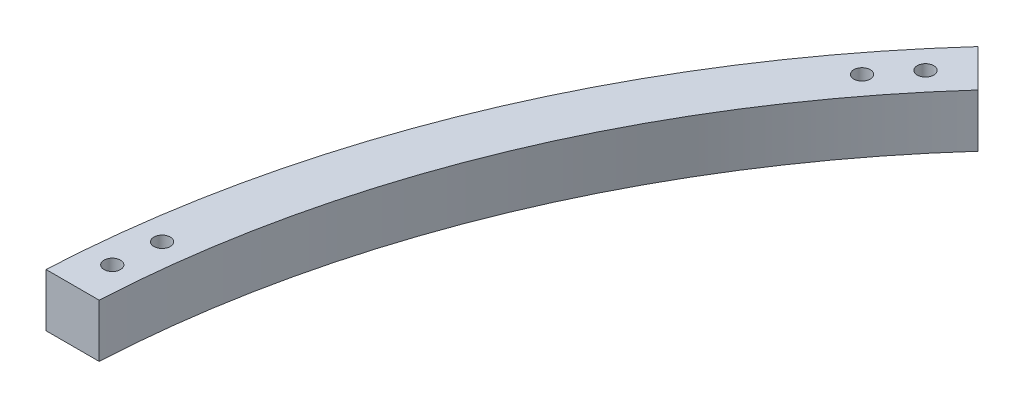
SolidWorks part; units mm, degrees
ref_plane "Front Plane" through (0, 0, 0) normal (0, 0, 1) x (1, 0, 0)
ref_plane "Top Plane" through (0, 0, 0) normal (0, 1, 0) x (1, 0, 0)
ref_plane "Right Plane" through (0, 0, 0) normal (1, 0, 0) x (0, 0, -1)
sketch "Sketch1" plane through (0, 0, 0) normal (0, 1, 0) x (1, 0, 0)
  line L1 (0, 200) -> (0, -200) construction
  line L6 (-200, 0) -> (200, 0) construction
  line L7 (-10, 199.7498) -> (-10, -199.7498) construction
  line L12 (-10, 199.7498) -> (-10, 189.7367)
  line L13 (-199.7498, 10) -> (199.7498, 10) construction
  line L14 (-199.7498, 10) -> (-189.7367, 10)
  line L15 (-141.4214, 141.4214) -> (141.4214, -141.4214) construction
  line L16 (-148.3155, 134.1734) -> (134.1734, -148.3155)
  arc A3 (-10, 199.7498) -> (-199.7498, 10) centre (0, 0) ccw
  arc A4 (-10, 189.7367) -> (-189.7367, 10) centre (0, 0) ccw
  arc A5 (-190, 0) -> (-189.7367, 10) centre (0, 0) ccw construction
  arc A6 (-200, 0) -> (-199.7498, 10) centre (0, 0) ccw construction
  circle A7 centre (0, 0) radius 195 construction
  dimension "D1" = 190
  dimension "D2" = 200
  dimension "D4" = 10
  dimension "D5" = 5
  dimension "D3" = 10
  dimension "D6" = 10
sketch "Sketch14" [suppressed] plane through (0, 0, 0) normal (0, 1, 0) x (1, 0, 0)
  line L0 (-200, 10) -> (200, 10) construction
  line L1 (-10, 200) -> (-10, -200) construction
  line L2 (-200, 10) -> (-189.7367, 10)
  line L3 (-10, 200) -> (-10, 189.7367)
  circle A0 centre (0, 0) radius 200 construction
  circle A1 centre (0, 0) radius 190 construction
  arc A2 (-10, 199.7498) -> (-199.7498, 10) centre (0, 0) ccw
  arc A3 (-10, 189.7367) -> (-189.7367, 10) centre (0, 0) ccw
sketch "roll" plane through (0, 0, 0) normal (0, 1, 0) x (1, 0, 0)
  line L0 (0, -195) -> (0, 195) construction
  dimension "D1" = 390
ref_axis "Axis1" through (0, -148.0362, 0) along (0, 1, 0)
extrude "base" add sketch "Sketch1" along normal mid plane 10 contours A4 L15 A3 L14 region at (-176.7216, 0, -73.2005)
sketch "Sketch25" plane through (0, 5, 0) normal (0, 1, 0) x (1, 0, 0)
  line L0 (-200, 0) -> (200, 0) construction
  line L1 (0, 200) -> (0, -200) construction
  line L2 (-200, 0) -> (200, 0)
  line L3 (0, 200) -> (0, -200)
  line L4 (0, 0) -> (-194.258, 16.9954) construction
  line L5 (0, 0) -> (-193.3317, 25.4526) construction
  line L6 (-141.4214, 141.4214) -> (141.4214, -141.4214) construction
  line L7 (-141.4214, 141.4214) -> (141.4214, -141.4214)
  line L8 (0, 0) -> (-149.3787, 125.3436) construction
  line L9 (0, 0) -> (-154.7039, 118.7085) construction
  circle A0 centre (0, 0) radius 195 construction
  circle A1 centre (0, 0) radius 195 construction
  dimension "D1" = 5
  dimension "D2" = 7.5
  dimension "D3" = 5
  dimension "D4" = 7.5
ref_plane "Plane1" through (0, 0, 0) normal (0.7071, 0, -0.7071) x (0.7071, 0, 0.7071)
hole_wizard "Ø3.1 (3.1) Diameter Hole1" positions "Sketch28" profile "Sketch29" hole size "Ø3.1" standard "ISO" end condition through all
sketch "Sketch28" plane through (0, 5, 0) normal (0, 1, 0) x (1, 0, 0)
  point P0 (-194.258, 16.9954)
  point P3 (-149.3787, 125.3436)
  point P6 (-154.7039, 118.7085)
  point P9 (-193.3317, 25.4526)
sketch "Sketch29" plane through (-194.258, 5, -16.9954) normal (1, 0, 0) x (0, 0, 1)
  line L0 (0, 0) -> (0, 10)
  line L1 (0, 10) -> (1.55, 10)
  line L2 (1.55, 10) -> (1.55, 0)
  line L5 (1.55, 0) -> (0, 0)
  line L11 (0, -6.35) -> (0, 107.95) construction
  dimension "Thru Hole Dia." = 3.1
  dimension "Thru Hole Depth" = 10
